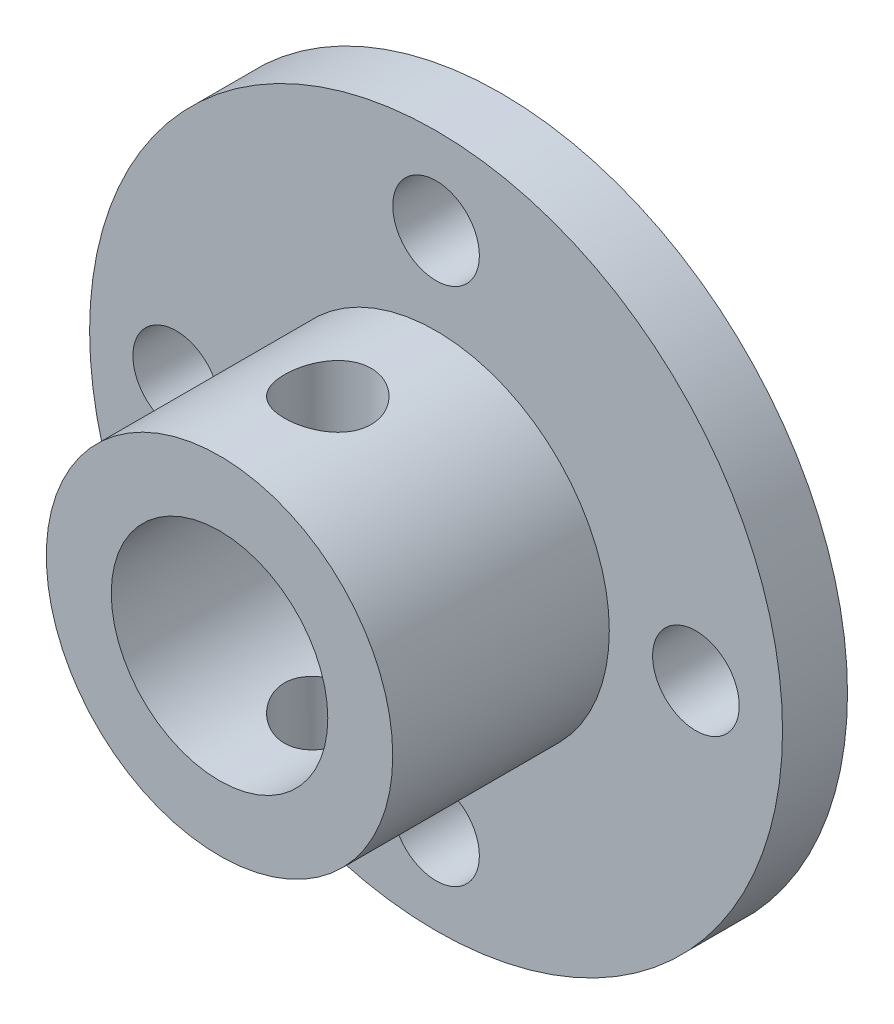
SolidWorks part; units mm, degrees
ref_plane "前视基准面" through (0, 0, 0) normal (0, 0, 1) x (1, 0, 0)
ref_plane "上视基准面" through (0, 0, 0) normal (0, 1, 0) x (1, 0, 0)
ref_plane "右视基准面" through (0, 0, 0) normal (1, 0, 0) x (0, 0, -1)
sketch "草图2" plane through (0, 0, 0) normal (0, 0, 1) x (1, 0, 0)
  circle A0 centre (0, 0) radius 16
  circle A1 centre (0, 0) radius 12 construction
  circle A2 centre (0, 0) radius 5
  circle A3 centre (0, -12) radius 2
  circle A4 centre (-12, 0) radius 2
  circle A5 centre (0, 12) radius 2
  circle A6 centre (12, 0) radius 2
  dimension "D1" = 24
  dimension "D2" = 10
  dimension "D3" = 4
  dimension "D5" = 32
  dimension "D4" = 4
extrude "凸台-拉伸1" add sketch "草图2" along normal blind 3
sketch "草图3" plane through (0, 0, 3) normal (0, 0, 1) x (1, 0, 0)
  circle A0 centre (0, 0) radius 5
  circle A1 centre (0, 0) radius 8
  dimension "D1" = 16
extrude "凸台-拉伸2" add sketch "草图3" along normal blind 10
sketch "草图4" plane through (0, 0, 0) normal (0, 1, 0) x (1, 0, 0)
  line L0 (0, 0) -> (0, -13) construction
  line L1 (-8, -13) -> (8, -13) construction
  circle A0 centre (0, -8) radius 2
  dimension "D1" = 4
  dimension "D2" = 5
extrude "切除-拉伸1" cut sketch "草图4" against normal blind 10 and the other way blind 10
